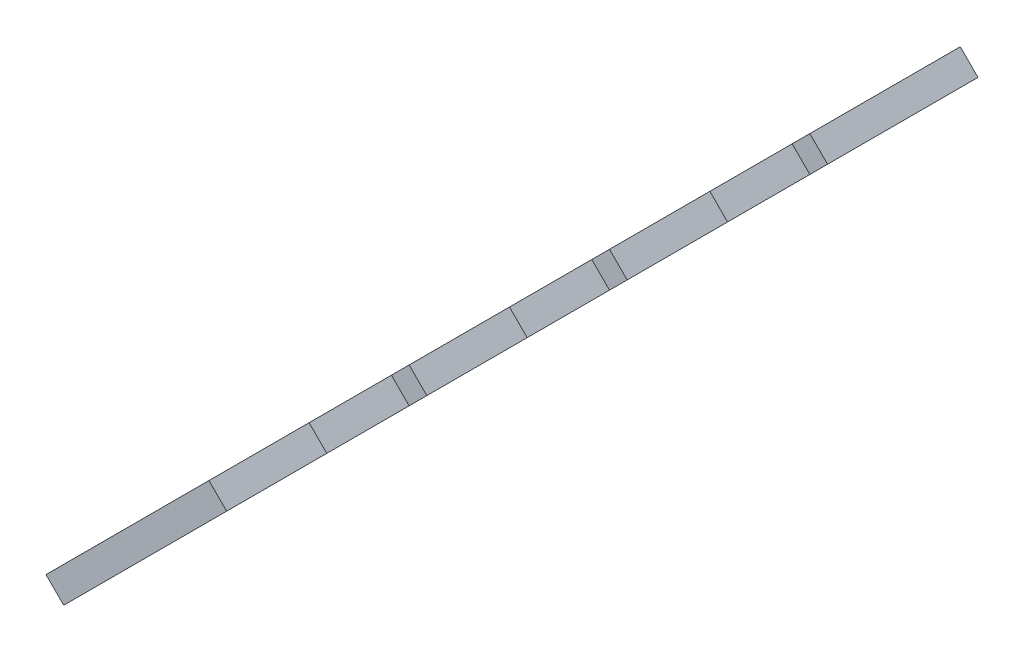
SolidWorks part; units mm, degrees
ref_plane "Front Plane" through (0, 0, 0) normal (0, 0, 1) x (1, 0, 0)
ref_plane "Top Plane" through (0, 0, 0) normal (0, 1, 0) x (1, 0, 0)
ref_plane "Right Plane" through (0, 0, 0) normal (1, 0, 0) x (0, 0, -1)
sketch "Sketch1" plane through (0, 0, 0) normal (0, 0, 1) x (1, 0, 0)
  line L0 (-108.2121, 4.5408) -> (-66.9029, 45.85)
  line L1 (-108.2121, 4.5408) -> (-112.7022, 9.0309)
  line L2 (-66.9029, 45.85) -> (-71.393, 50.3401)
  line L3 (-112.7022, 9.0309) -> (-71.393, 50.3401)
  line L4 (-76.7812, -26.8901) -> (-72.2911, -22.4) construction
extrude "Boss-Extrude1" add sketch "Sketch1" along normal up to surface (190.5 mm away)
sketch "Sketch2" plane through (-60.8666, 60.8666, 0) normal (-0.7071, 0.7071, 0) x (0, 0, 1)
  line L0 (190.5, -14.8867) -> (0, -14.8867) construction
  line L1 (165.1, -21.2367) -> (139.7412, -21.2367)
  line L2 (165.1, -21.2367) -> (165.1, -14.8867)
  line L3 (165.1, -14.8867) -> (139.7412, -14.8867)
  line L4 (139.7412, -21.2367) -> (139.7412, -14.8867)
  line L5 (190.5, -73.3067) -> (0, -73.3067) construction
  line L6 (165.1, -66.9567) -> (139.7412, -66.9567)
  line L7 (165.1, -66.9567) -> (165.1, -73.3067)
  line L8 (165.1, -73.3067) -> (139.7412, -73.3067)
  line L9 (139.7412, -66.9567) -> (139.7412, -73.3067)
  dimension "D1" = 25.3588
extrude "Cut-Extrude1" cut sketch "Sketch2" against normal blind 6.35
pattern_linear "LPattern1" count 3 spacing 50.8 along (0, 0, -1) of "Cut-Extrude1"
sketch "Sketch3" plane through (0, 0, 0) normal (0, 0, -1) x (-1, 0, 0)
  line L0 (92.4966, 20.2562) -> (96.9868, 24.7464)
  line L1 (108.2121, 4.5408) -> (66.9029, 45.85) construction
  line L2 (71.393, 50.3401) -> (112.7022, 9.0309) construction
  line L3 (96.9868, 24.7464) -> (88.0065, 33.7266)
  line L4 (88.0065, 33.7266) -> (83.5144, 29.2385)
  line L5 (187.6134, 29.2385) -> (16.1634, 29.2385) construction
  line L6 (83.5144, 29.2385) -> (92.4966, 20.2562)
  dimension "D1" = 12.7
  dimension "D2" = 6.35
  dimension "D3" = 22.225
extrude "Boss-Extrude2" add sketch "Sketch3" along normal blind 6.35
